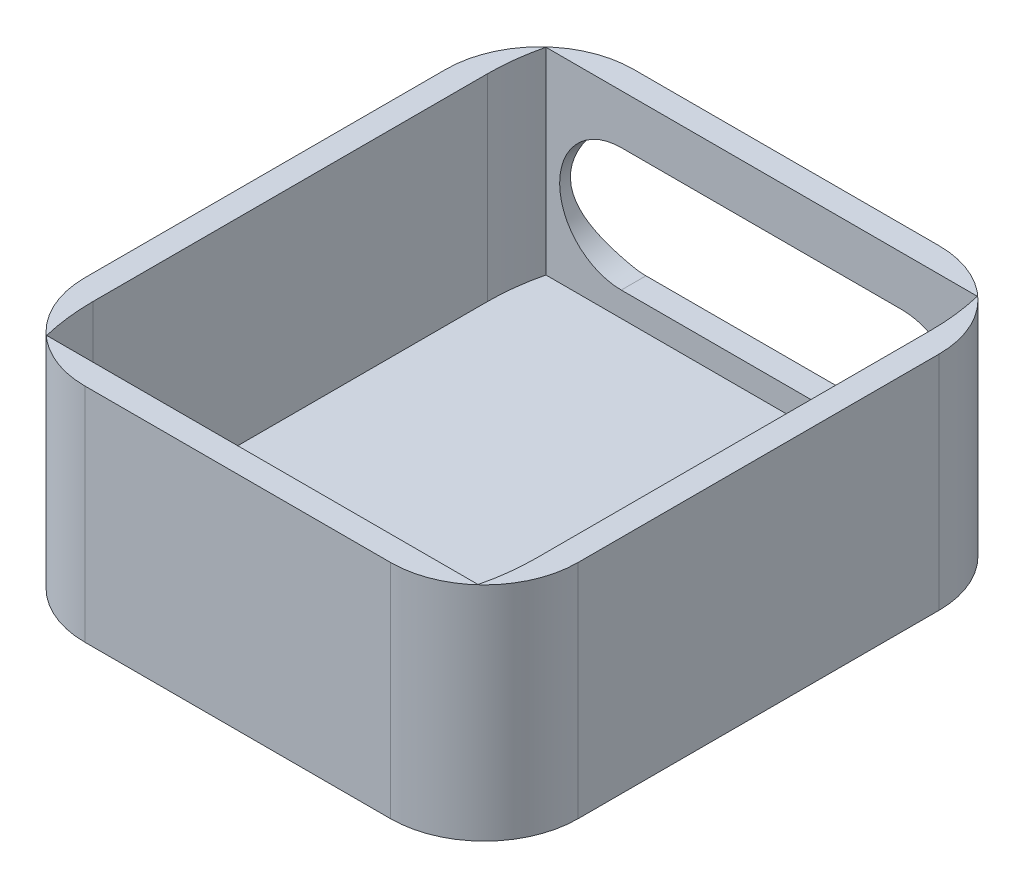
SolidWorks part; units mm, degrees
ref_plane "Front Plane" through (0, 0, 0) normal (0, 0, 1) x (1, 0, 0)
ref_plane "Top Plane" through (0, 0, 0) normal (0, 1, 0) x (1, 0, 0)
ref_plane "Right Plane" through (0, 0, 0) normal (1, 0, 0) x (0, 0, -1)
sketch "Sketch2" plane through (0, 0, 0) normal (0, 1, 0) x (1, 0, 0)
  line L0 (0, -101.6) -> (0, 101.6) construction
  line L1 (-127, -101.6) -> (-127, 101.6)
  line L2 (127, -101.6) -> (127, 101.6)
  line L3 (0, 228.6) -> (0, -228.6) construction
  line L4 (-120.65, 141.2557) -> (120.65, 141.2557)
  line L5 (127, 0) -> (-127, 0) construction
  line L6 (-120.65, -141.2557) -> (120.65, -141.2557)
  arc A0 (-127, -101.6) -> (127, -101.6) centre (0, -101.6) ccw
  arc A1 (127, 101.6) -> (-127, 101.6) centre (0, 101.6) ccw
  point P3 (0, 0)
  dimension "D2" = 254
  dimension "D1" = 203.2
  dimension "D3" = 241.3
extrude "Boss-Extrude1" add sketch "Sketch2" along normal blind 114.3 contours L2 A1 L4 L1 A0 region at (0, 0, 0)
shell "Shell1" thickness 12.7 removed face at (0, 114.3, 0)
sketch "Sketch3" plane through (0, 0, 0) normal (0, 0, 1) x (1, 0, 0)
  line L0 (-72.269, 57.15) -> (72.269, 57.15) construction
  line L1 (-72.269, 82.55) -> (72.269, 82.55)
  line L2 (-72.269, 31.75) -> (72.269, 31.75)
  line L5 (0, 0) -> (0, 114.3) construction
  line L7 (-72.269, 88.9) -> (72.269, 88.9)
  line L8 (-72.269, 25.4) -> (72.269, 25.4)
  arc A0 (-72.269, 82.55) -> (-72.269, 31.75) centre (-72.269, 57.15) ccw
  arc A1 (72.269, 31.75) -> (72.269, 82.55) centre (72.269, 57.15) ccw
  arc A2 (72.269, 25.4) -> (72.269, 88.9) centre (72.269, 57.15) ccw
  arc A3 (-72.269, 88.9) -> (-72.269, 25.4) centre (-72.269, 57.15) ccw
  point P2 (0, 57.15)
  dimension "D1" = 50.8
  dimension "D3" = 6.35
extrude "Cut-Extrude1" cut sketch "Sketch3" against normal through all contours L2 A1 L1 A0 | L7 A3 L8 A2 A1 L2 A0 L1 region at (0, 57.15, 0) region at (0, 86.7249, 0)
fillet "Fillet1" radius 48.26 2 edges at (120.65, 57.15, 141.2557) (-120.65, 57.15, 141.2557)
fillet "Fillet2" radius 48.26 2 edges at (120.65, 57.15, -141.2557) (-120.65, 57.15, -141.2557)
